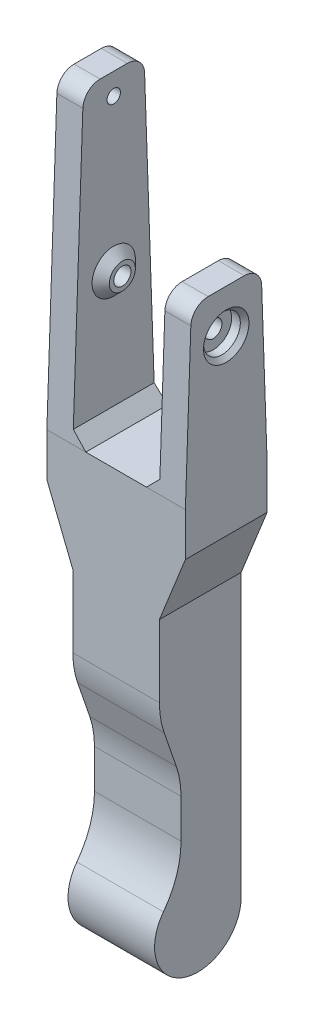
SolidWorks part; units mm, degrees
ref_plane "Front Plane" through (0, 0, 0) normal (0, 0, 1) x (1, 0, 0)
ref_plane "Top Plane" through (0, 0, 0) normal (0, 1, 0) x (1, 0, 0)
ref_plane "Right Plane" through (0, 0, 0) normal (1, 0, 0) x (0, 0, -1)
sketch "Sketch1" plane through (0, 0, 0) normal (1, 0, 0) x (0, 0, -1)
  line L0 (-9.4445, -30) -> (-7, 40)
  line L1 (-7, 40) -> (7, 40)
  line L2 (7, 40) -> (9.4445, -30)
  line L3 (9.4445, -30) -> (-9.4445, -30)
  circle A0 centre (0, 0) radius 2
  point P5 (0, -30)
  point P8 (0, 40)
  dimension "D1" = 4
  dimension "D2" = 40
  dimension "D3" = 92
  dimension "D4" = 30
  dimension "D5" = 14
extrude "Boss-Extrude1" add sketch "Sketch1" along normal blind 6
sketch "Sketch2" plane through (0, 0, 0) normal (-1, 0, 0) x (0, 0, 1)
  circle A0 centre (0, 0) radius 4.25
  dimension "D1" = 8.5
extrude "Cut-Extrude1" cut sketch "Sketch2" against normal blind 3
sketch "Sketch3" plane through (0, 0, 0) normal (-1, 0, 0) x (0, 0, 1)
  line L1 (-9.4445, -30) -> (9.4445, -30)
  line L2 (-9.4445, -30) -> (-9.4445, -40)
  line L3 (-9.4445, -40) -> (9.4445, -40)
  line L4 (9.4445, -30) -> (9.4445, -40)
  dimension "D1" = 10
extrude "Boss-Extrude2" add sketch "Sketch3" against normal blind 32
sketch "Sketch4" plane through (32, 0, 0) normal (1, 0, 0) x (0, 0, -1)
  line L0 (9.4445, -30) -> (-9.4445, -30)
  line L1 (-9.4445, -30) -> (-8.0476, 10)
  line L2 (-7, 40) -> (-9.4445, -30) construction
  line L3 (-8.0476, 10) -> (8.0476, 10)
  line L12 (9.4445, -30) -> (7, 40) construction
  line L13 (8.0476, 10) -> (9.4445, -30)
  circle A0 centre (0, 0) radius 2 construction
  circle A1 centre (0, 0) radius 2
  dimension "D1" = 10
extrude "Boss-Extrude3" add sketch "Sketch4" against normal blind 6
fillet "Fillet1" radius 4 4 edges at (3, 40, -7) (3, 40, 7) (29, 10, -8.0476) (29, 10, 8.0476)
extrude "Cut-Extrude2" cut sketch "Sketch2<2>" along normal blind 3 from surface starting at face at (32, -13.2632, 0)
sketch "Sketch2<2>" plane through (0, 0, 0) normal (-1, 0, 0) x (0, 0, 1) same geometry as "Sketch2"
chamfer "Chamfer1" distance 1 angle 45 2 edges at (0, 0, 4.25) (32, 0, 4.25)
chamfer "Chamfer2" distance 3 angle 45 2 edges at (6, -30, 0) (26, -30, 0)
sketch "Sketch5" plane through (6, 0, 0) normal (1, 0, 0) x (0, 0, -1)
  circle A0 centre (0, 0) radius 2 construction
  circle A1 centre (0, 0) radius 2
  circle A2 centre (0, 0) radius 3
  dimension "D1" = 1
extrude "Boss-Extrude4" add sketch "Sketch5" along normal blind 2
extrude "Boss-Extrude5" add sketch "Sketch5<2>" against normal blind 2 from surface starting at face at (26, 0, -2)
sketch "Sketch5<2>" plane through (6, 0, 0) normal (1, 0, 0) x (0, 0, -1) same geometry as "Sketch5"
chamfer "Chamfer4" distance 2 angle 45 2 edges at (26, 0, 3) (6, 0, 3)
sketch "Sketch7" plane through (0, 0, -9.4445) normal (0, 0, -1) x (-1, 0, 0)
  line L0 (-32, -40) -> (-26, -55)
  line L1 (-26, -55) -> (-26, -60)
  line L2 (-6, -60) -> (-6, -55)
  line L3 (-6, -55) -> (0, -40)
  line L4 (-6, -60) -> (-26, -60)
  line L5 (-32, -40) -> (0, -40) construction
  line L6 (-16, -60) -> (-16, -40) construction
  line L7 (0, -40) -> (-32, -40)
  dimension "D1" = 20
  dimension "D2" = 5
  dimension "D3" = 15
extrude "Boss-Extrude6" add sketch "Sketch7" against normal up to surface (18.8889 mm away) up to face at (16, -33.3333, 9.4445)
sketch "Sketch8" plane through (26, 0, 0) normal (1, 0, 0) x (0, 0, -1)
  line L1 (9.4445, -60) -> (-9.4445, -60)
  line L2 (-9.4445, -60) -> (-9.4445, -90)
  line L5 (9.4445, -60) -> (9.4445, -120)
  line L6 (-9.4445, -90) -> (-4.4445, -90)
  line L7 (-4.4445, -90) -> (-4.4445, -110.7872)
  arc A2 (-4.4445, -110.7872) -> (9.4445, -120) centre (-0.5555, -120) ccw
  point P10 (9.4445, -90)
  dimension "D1" = 60
  dimension "D2" = 5
  dimension "D3" = 20
extrude "Boss-Extrude7" add sketch "Sketch8" against normal up to surface (20 mm away) up to face at (6, -57.5, 0)
chamfer "Chamfer5" distance 15 angle 19 1 edges at (16, -90, 9.4445) first distance on face at (16, -49, 9.4445)
fillet "Fillet2" radius 20 3 edges at (16, -110.7872, 4.4445) (16, -89.5211, 4.4445) (16, -75, 9.4445)
sketch "Sketch9" plane through (6, 0, 0) normal (1, 0, 0) x (0, 0, -1)
  circle A0 centre (0, 35) radius 1.55
  dimension "D1" = 35
  dimension "D2" = 3.1
extrude "Cut-Extrude3" cut sketch "Sketch9" against normal up to surface (6 mm away) up to face at (0, 0, 5.25)
sketch "Sketch10" plane through (0, 0, 0) normal (-1, 0, 0) x (0, 0, 1)
  circle A0 centre (0, 35) radius 1.55 construction
  circle A1 centre (0, 35) radius 1.55
  circle A2 centre (0, 35) radius 3.25
  dimension "D1" = 6.5
extrude "Cut-Extrude4" cut sketch "Sketch10" against normal blind 3
chamfer "Chamfer6" distance 1 angle 45 1 edges at (0, 35, 3.25)
